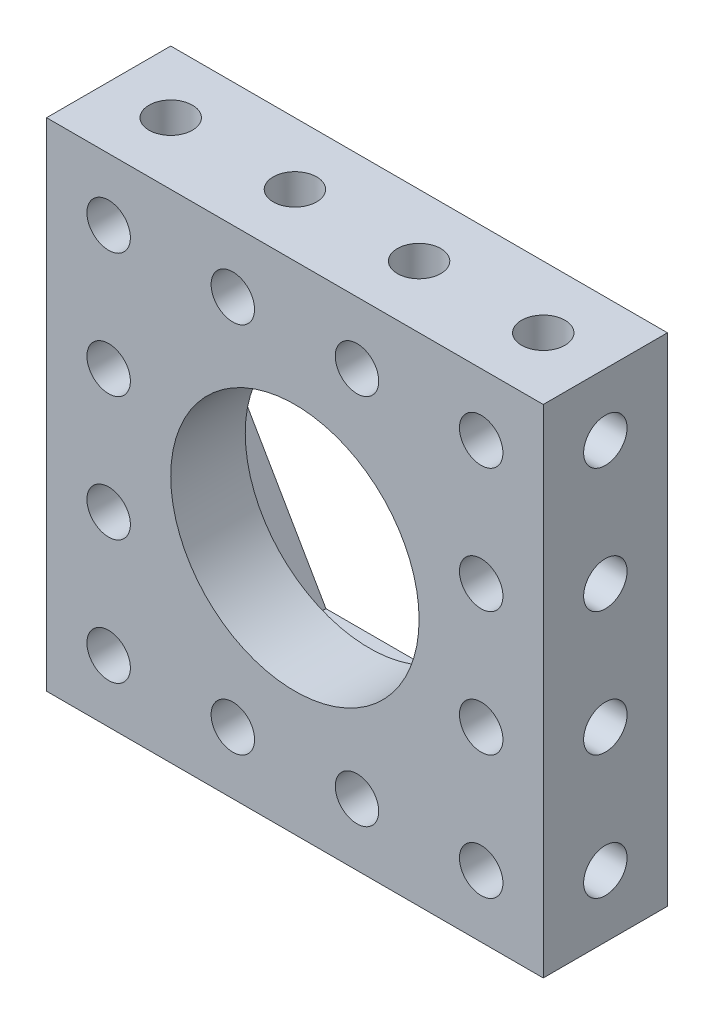
SolidWorks part; units mm, degrees
ref_plane "Plan de face" through (0, 0, 0) normal (0, 0, 1) x (1, 0, 0)
ref_plane "Plan de dessus" through (0, 0, 0) normal (0, 1, 0) x (1, 0, 0)
ref_plane "Plan de droite" through (0, 0, 0) normal (1, 0, 0) x (0, 0, -1)
sketch "Esquisse1" plane through (0, 0, 0) normal (0, 0, 1) x (1, 0, 0)
  line L0 (0, 20) -> (40, 20) construction
  line L1 (0, 0) -> (40, 0)
  line L2 (0, 0) -> (0, 40)
  line L3 (0, 40) -> (40, 40)
  line L4 (40, 0) -> (40, 40)
  line L5 (20, 40) -> (20, 0) construction
  line L7 (35, 20) -> (27.5, 32.9904)
  line L8 (27.5, 32.9904) -> (12.5, 32.9904)
  line L9 (12.5, 32.9904) -> (5, 20)
  line L10 (5, 20) -> (12.5, 7.0096)
  line L11 (12.5, 7.0096) -> (27.5, 7.0096)
  line L12 (27.5, 7.0096) -> (35, 20)
  circle A0 centre (20, 20) radius 10
  circle A1 centre (20, 20) radius 12.9904 construction
  point P11 (20, 7.0096)
  dimension "D1" = 20
  dimension "D2" = 40
  dimension "D3" = 40
  dimension "D4" = 15
extrude "Boss.-Extru.1" add sketch "Esquisse1" along normal blind 10 contours L1 L4 L3 L2 L12 L11 L10 L9 L8 L7 region at (0.5657, 20, 0)
extrude "Boss.-Extru.2" add sketch "Esquisse1<3>" along normal up to surface (10 mm away) from offset 4 contours L11 L12 L7 L8 L9 L10 A0 region at (30.9063, 13.7032, 0) up to face at (20, 20, 10)
sketch "Esquisse1<3>" plane through (0, 0, 0) normal (0, 0, 1) x (1, 0, 0) same geometry as "Esquisse1"
ref_plane "Plan1" through (0, 20, 0) normal (0, -1, 0) x (-1, 0, 0)
sketch "Esquisse6" plane through (0, 20, 0) normal (0, -1, 0) x (-1, 0, 0)
  line L0 (0, -10) -> (0, 0) construction
  circle A0 centre (-5, -5) radius 1.75
  circle A1 centre (-15, -5) radius 1.75
  circle A2 centre (-25, -5) radius 1.75
  circle A3 centre (-35, -5) radius 1.75
  circle A4 centre (-45, -5) radius 1.75
  point P4 (0, -5)
  dimension "D1" = 5
  dimension "D2" = 3.5
  dimension "D3" = 5
extrude "Enlèv. mat.-Extru.3" cut sketch "Esquisse6" against normal through all both and the other way through all
extrude "Enlèv. mat.-Extru.7" cut sketch "Esquisse6<6>" along normal blind 6 from surface contours A1 | A2 | A3 rebuild error yes
sketch "Esquisse6<6>" plane through (0, 20, 0) normal (0, -1, 0) x (-1, 0, 0) same geometry as "Esquisse6"
ref_plane "Plan2" through (20, 0, 0) normal (1, 0, 0) x (0, 0, -1)
sketch "Esquisse9" plane through (20, 0, 0) normal (1, 0, 0) x (0, 0, -1)
  line L1 (-5, 42.6891) -> (-5, 19.7522) construction
  line L2 (-10, 40) -> (0, 40) construction
  circle A0 centre (-5, 35) radius 1.75
  circle A1 centre (-5, 25) radius 1.75
  circle A2 centre (-5, 15) radius 1.75
  circle A3 centre (-5, 5) radius 1.75
  point P6 (-5, 40)
  dimension "D1" = 3.5
  dimension "D2" = 5
  dimension "D3" = 4
extrude "Enlèv. mat.-Extru.10" cut sketch "Esquisse9" against normal through all and the other way through all
sketch "Esquisse11" plane through (0, 0, 10) normal (0, 0, 1) x (1, 0, 0)
  line L0 (0, 0) -> (0, 40) construction
  line L1 (0, 0) -> (40, 0) construction
  circle A0 centre (5, 5) radius 1.75
  circle A1 centre (15, 5) radius 1.75
  circle A2 centre (25, 5) radius 1.75
  circle A3 centre (35, 5) radius 1.75
  circle A4 centre (25, 15) radius 1.75
  circle A5 centre (15, 15) radius 1.75 construction
  circle A6 centre (35, 15) radius 1.75
  circle A7 centre (25, 25) radius 1.75
  circle A8 centre (35, 25) radius 1.75
  circle A9 centre (15, 25) radius 1.75 construction
  circle A10 centre (25, 35) radius 1.75
  circle A11 centre (35, 35) radius 1.75
  circle A13 centre (15, 35) radius 1.75
  circle A17 centre (5, 15) radius 1.75
  circle A18 centre (5, 25) radius 1.75
  circle A19 centre (5, 35) radius 1.75
  dimension "D1" = 3.5
  dimension "D2" = 5
  dimension "D3" = 5
  dimension "D4" = 4
  dimension "D5" = 4
extrude "Enlèv. mat.-Extru.13" cut sketch "Esquisse11" against normal through all
sketch "Esquisse12" plane through (0, 0, 0) normal (0, 0, -1) x (-1, 0, 0)
  line L13 (-35, 20) -> (-27.5, 7.0096)
  line L14 (-27.5, 32.9904) -> (-35, 20)
  line L15 (-12.5, 32.9904) -> (-27.5, 32.9904)
  line L16 (-5, 20) -> (-12.5, 32.9904)
  line L17 (-12.5, 7.0096) -> (-5, 20)
  line L18 (-27.5, 7.0096) -> (-12.5, 7.0096)
  line L19 (-35, 20) -> (-27.5, 7.0096)
  line L20 (-27.5, 32.9904) -> (-35, 20)
  line L21 (-12.5, 32.9904) -> (-27.5, 32.9904)
  line L22 (-5, 20) -> (-12.5, 32.9904)
  line L23 (-12.5, 7.0096) -> (-5, 20)
  line L24 (-27.5, 7.0096) -> (-12.5, 7.0096)
  circle A0 centre (-20, 20) radius 10
  arc A1 (-10.6566, 16.4361) -> (-10.6566, 23.5639) centre (-20, 20) ccw construction
  dimension "D1" = 0
extrude "Boss.-Extru.3" add sketch "Esquisse12" against normal up to surface (10 mm away) from vertex up to face at (16.75, 35, 10) starting at point (12.5, 32.9904, 4)
